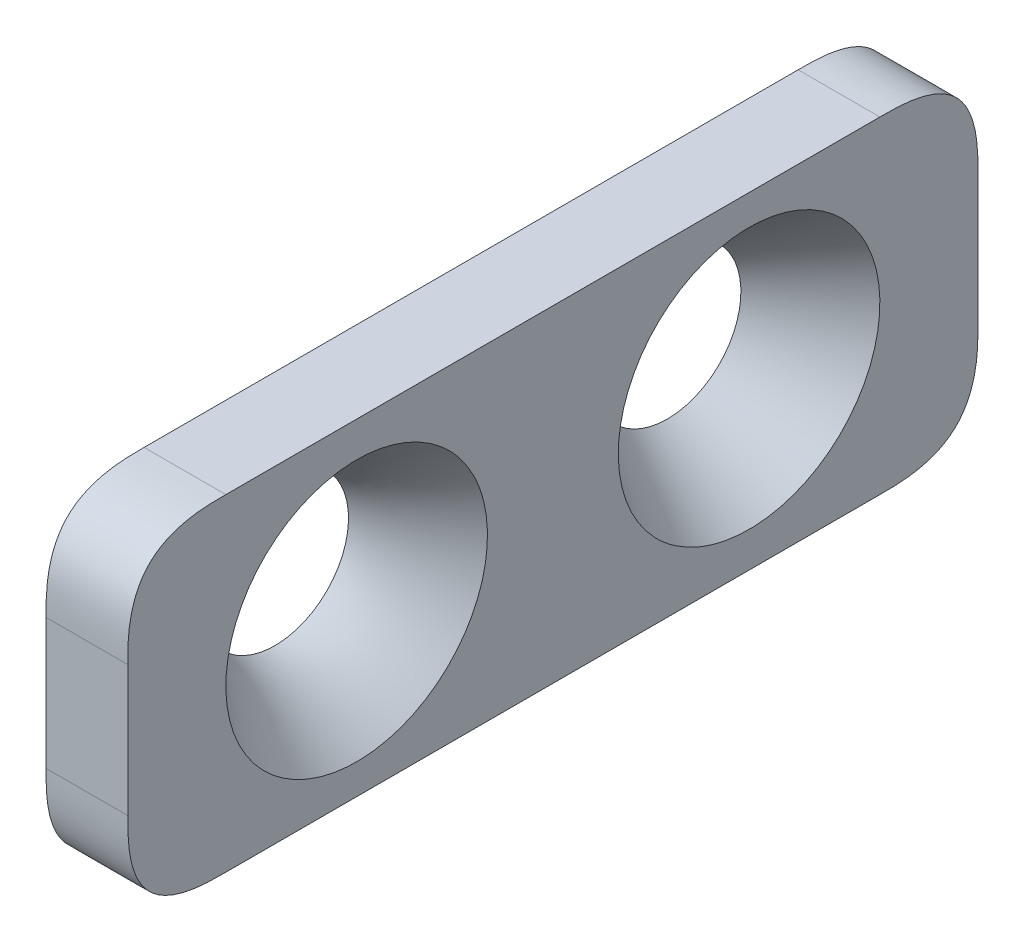
SolidWorks part; units mm, degrees
ref_plane "Front Plane" through (0, 0, 0) normal (0, 0, 1) x (1, 0, 0)
ref_plane "Top Plane" through (0, 0, 0) normal (0, 1, 0) x (1, 0, 0)
ref_plane "Right Plane" through (0, 0, 0) normal (1, 0, 0) x (0, 0, -1)
other "Center of Mass"
sketch "Sketch1" plane through (0, 0, 0) normal (1, 0, 0) x (0, 0, -1)
  line L1 (0, 0) -> (26, 0)
  line L2 (0, 0) -> (0, 10)
  line L3 (0, 10) -> (26, 10)
  line L4 (26, 0) -> (26, 10)
  dimension "D1" = 26
  dimension "D2" = 10
extrude "Boss-Extrude1" add sketch "Sketch1" along normal blind 2.5
fillet "Fillet1" radius 3 4 edges at (1.25, 10, 0) (1.25, 0, 0) (1.25, 0, -26) (1.25, 10, -26) curvature continuous yes
sketch "Sketch3" plane through (2.5, 0, 0) normal (1, 0, 0) x (0, 0, -1)
  line L0 (0, 5) -> (26, 5) construction
  line L1 (0, 7) -> (0, 3) construction
  line L2 (26, 3) -> (26, 7) construction
  line L3 (7, 5.732) -> (7, 4.1139) construction
  line L4 (19, 6.0403) -> (19, 4.1139) construction
  line L6 (23, 10) -> (3, 10) construction
  circle A1 centre (7, 4.9229) radius 4
  circle A2 centre (19, 5.0771) radius 4
  point P8 (7, 4.9229)
  point P11 (19, 5.0771)
  dimension "D3" = 8
  dimension "D4" = 8
  dimension "D1" = 7
  dimension "D2" = 7
  dimension "D5" = 4.9229
  dimension "D6" = 5.0771
  dimension "D9" = 5.8861
  dimension "D10" = 5.8861
sketch "Sketch4" plane through (0, 0, 0) normal (-1, 0, 0) x (0, 0, 1)
  line L0 (0, 5) -> (-26, 5) construction
  line L1 (0, 7) -> (0, 3) construction
  line L2 (-26, 3) -> (-26, 7) construction
  line L3 (-7, 5) -> (-7, 4.9229) construction
  line L4 (-7, 5.732) -> (-7, 4.1139) construction
  circle A0 centre (-7, 5) radius 2.25
  circle A1 centre (-19, 5) radius 2.25
  dimension "D1" = 7
  dimension "D2" = 7
loft "Cut-Loft1" cut section "Sketch4" section "Sketch3" connector at (0, 5.2272, -4.7615) connector at (2.5, 2.8116, -3.6026)
loft "Cut-Loft2" cut section "Sketch4<5>" section "Sketch3<6>" connector at (0, 6.928, -20.1599) connector at (2.5, 8.5991, -20.8961)
sketch "Sketch4<5>" plane through (0, 0, 0) normal (-1, 0, 0) x (0, 0, 1) same geometry as "Sketch4"
sketch "Sketch3<6>" plane through (2.5, 0, 0) normal (1, 0, 0) x (0, 0, -1) same geometry as "Sketch3"
sketch3d "3DSketch1"
  point P0 (1.25, 5, 0)
